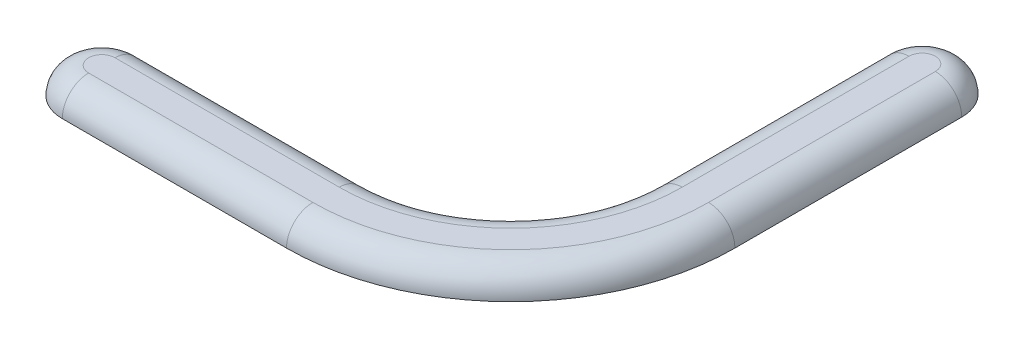
SolidWorks part; units mm, degrees
ref_plane "Alzado" through (0, 0, 0) normal (0, 0, 1) x (1, 0, 0)
ref_plane "Planta" through (0, 0, 0) normal (0, 1, 0) x (1, 0, 0)
ref_plane "Vista lateral" through (0, 0, 0) normal (1, 0, 0) x (0, 0, -1)
sketch "Croquis1" plane through (0, 0.4561, 0) normal (0, 1, 0) x (1, 0, 0)
  line L1 (41.2064, -92.8368) -> (41.2064, -93.7368) construction
  line L12 (42.1064, -97.2104) -> (42.1064, -60.4463) construction
  line L13 (40.8564, -97.2104) -> (40.8564, -60.4463) construction
  line L14 (-3.5078, -102.7463) -> (35.3206, -102.7463) construction
  line L15 (42.1064, -97.2104) -> (42.1064, -60.4463) construction
  line L16 (40.8564, -97.2104) -> (40.8564, -60.4463) construction
  line L17 (-3.5078, -102.7463) -> (35.3206, -102.7463) construction
  line L18 (-3.5078, -103.9963) -> (35.3206, -103.9963) construction
  line L19 (-3.5078, -103.9963) -> (35.3206, -103.9963) construction
  line L20 (31.9064, -103.9963) -> (37.0064, -103.9963)
  line L21 (42.1064, -98.8963) -> (42.1064, -93.7368)
  line L22 (31.9064, -102.1963) -> (37.0064, -102.1963)
  line L23 (40.3064, -98.8963) -> (40.3064, -93.7368)
  line L26 (37.0064, -103.9963) -> (37.0064, -98.8963) construction
  line L27 (37.0064, -98.8963) -> (42.1064, -98.8963) construction
  line L28 (31.0064, -103.0963) -> (31.9064, -103.0963) construction
  arc A2 (42.1064, -98.8963) -> (37.0064, -103.9963) centre (37.0064, -98.8963) cw
  arc A3 (40.3064, -98.8963) -> (37.0064, -102.1963) centre (37.0064, -98.8963) cw
  arc A4 (31.9064, -103.9963) -> (31.9064, -102.1963) centre (31.9064, -103.0963) cw
  arc A5 (42.1064, -93.7368) -> (40.3064, -93.7368) centre (41.2064, -93.7368) ccw
  point P10 (41.2064, -92.8963)
  point P14 (40.3064, -98.8963)
  point P21 (31.0064, -103.0963)
  point P24 (41.2064, -92.8368)
  dimension "D1" = 11.1
  dimension "D3" = 1.8
  dimension "D4" = 1.8
extrude "Saliente-Extruir1" add sketch "Croquis1" along normal blind 0.6
fillet "Redondeo1" radius 0.6 8 edges at (40.3064, 1.0561, 96.3165) (39.3399, 1.0561, 101.2297) (42.1064, 1.0561, 96.3165) (40.6126, 1.0561, 102.5025) (41.2064, 1.0561, 92.8368) (34.4564, 1.0561, 102.1963) (31.0064, 1.0561, 103.0963) (34.4564, 1.0561, 103.9963)
